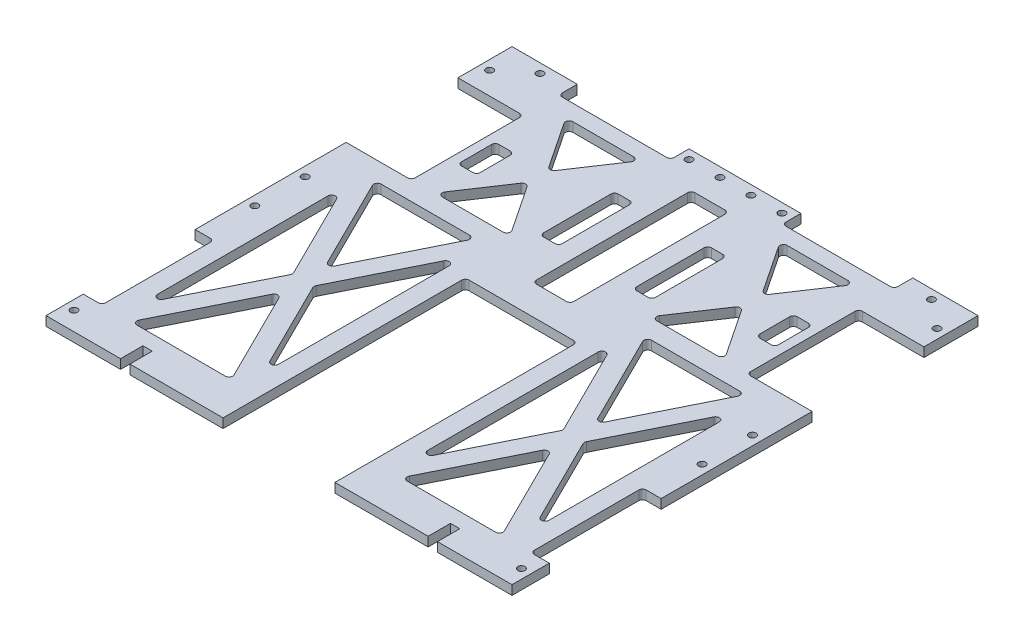
SolidWorks part; units mm, degrees
material "7050-T73510"
ref_plane "Front Plane" through (0, 0, 0) normal (0, 0, 1) x (1, 0, 0)
ref_plane "Top Plane" through (0, 0, 0) normal (0, 1, 0) x (1, 0, 0)
ref_plane "Right Plane" through (0, 0, 0) normal (1, 0, 0) x (0, 0, -1)
sketch "Sketch1" plane through (0, 0, 0) normal (0, 1, 0) x (1, 0, 0)
  line L0 (0, -55) -> (0, 55) construction
  line L1 (-158.75, -76.2) -> (158.75, -76.2)
  line L2 (-158.75, -76.2) -> (-158.75, 76.2)
  line L3 (-158.75, 76.2) -> (158.75, 76.2)
  line L4 (158.75, -76.2) -> (158.75, 76.2)
  line L5 (-158.75, -76.2) -> (158.75, 76.2) construction
  line L6 (-158.75, 76.2) -> (158.75, -76.2) construction
  line L7 (-158.75, -76.2) -> (-25.4, -76.2)
  line L8 (-158.75, -76.2) -> (-158.75, -241.3)
  line L9 (-158.75, -241.3) -> (-25.4, -241.3)
  line L10 (-25.4, -76.2) -> (-25.4, -241.3)
  line L11 (25.4, -76.2) -> (25.4, -241.3)
  line L12 (158.75, -241.3) -> (25.4, -241.3)
  line L13 (158.75, -76.2) -> (158.75, -241.3)
  line L14 (158.75, -76.2) -> (25.4, -76.2)
  line L15 (-38.1, -76.2) -> (-38.1, -241.3)
  line L16 (38.1, -76.2) -> (38.1, -241.3)
  point P0 (0, 0)
  dimension "D1" = 317.5
  dimension "D2" = 152.4
  dimension "D3" = 317.5
  dimension "D4" = 50.8
  dimension "D5" = 12.7
extrude "Boss-Extrude1" add sketch "Sketch1" along normal blind 6.35 contours L15 L1 L8 L9 | L14 L16 L12 L13 | L1 L7 L14 L4 L3 L2 region at (0, 0, 0) region at (-98.425, 0, 158.75) region at (98.425, 0, 158.75)
sketch "Sketch2" plane through (0, 6.35, 0) normal (0, 1, 0) x (1, 0, 0)
  line L0 (158.75, -241.3) -> (158.75, 76.2) construction
  line L1 (158.75, 39.37) -> (114.3, 39.37)
  line L2 (158.75, 39.37) -> (158.75, -36.83)
  line L3 (158.75, -36.83) -> (114.3, -36.83)
  line L4 (114.3, 39.37) -> (114.3, -36.83)
  line L5 (-158.75, 76.2) -> (158.75, 76.2) construction
  line L6 (158.75, -139.7) -> (146.05, -139.7)
  line L7 (158.75, -139.7) -> (158.75, -215.9)
  line L8 (158.75, -215.9) -> (146.05, -215.9)
  line L9 (146.05, -139.7) -> (146.05, -215.9)
  line L10 (0, -55) -> (0, 55) construction
  line L11 (-158.75, -215.9) -> (-146.05, -215.9)
  line L12 (-146.05, -139.7) -> (-146.05, -215.9)
  line L13 (-158.75, -139.7) -> (-146.05, -139.7)
  line L14 (-158.75, -139.7) -> (-158.75, -215.9)
  line L15 (-158.75, -36.83) -> (-114.3, -36.83)
  line L16 (-114.3, 39.37) -> (-114.3, -36.83)
  line L17 (-158.75, 39.37) -> (-114.3, 39.37)
  line L18 (-158.75, 39.37) -> (-158.75, -36.83)
  line L19 (-114.3, 63.5) -> (-38.1, 63.5)
  line L20 (114.3, 76.2) -> (38.1, 76.2)
  line L21 (114.3, 76.2) -> (114.3, 63.5)
  line L22 (114.3, 63.5) -> (38.1, 63.5)
  line L23 (38.1, 76.2) -> (38.1, 63.5)
  line L24 (-38.1, 76.2) -> (-38.1, 63.5)
  line L25 (-114.3, 76.2) -> (-38.1, 76.2)
  line L26 (-114.3, 76.2) -> (-114.3, 63.5)
  dimension "D1" = 44.45
  dimension "D2" = 12.7
  dimension "D3" = 76.2
  dimension "D4" = 76.2
  dimension "D5" = 36.83
  dimension "D6" = 215.9
  dimension "D7" = 76.2
  dimension "D8" = 12.7
  dimension "D9" = 76.2
extrude "Cut-Extrude1" cut sketch "Sketch2" against normal through all
sketch "Sketch4" plane through (0, 6.35, 0) normal (0, 1, 0) x (1, 0, 0)
  line L0 (38.1, -76.2) -> (38.1, -241.3) construction
  line L1 (50.8, -215.9) -> (133.35, -215.9)
  line L2 (50.8, -215.9) -> (50.8, -49.53)
  line L3 (50.8, -49.53) -> (133.35, -49.53)
  line L4 (133.35, -215.9) -> (133.35, -49.53)
  line L5 (146.05, -139.7) -> (146.05, -215.9) construction
  line L6 (158.75, -241.3) -> (38.1, -241.3) construction
  line L7 (50.8, -215.9) -> (133.35, -49.53) construction
  line L8 (50.8, -49.53) -> (133.35, -215.9) construction
  line L9 (133.35, -201.6135) -> (57.8887, -49.53)
  line L10 (126.2613, -215.9) -> (50.8, -63.8165)
  line L11 (50.8, -201.6135) -> (126.2613, -49.53)
  line L12 (57.8887, -215.9) -> (133.35, -63.8165)
  line L13 (114.3, -36.83) -> (158.75, -36.83) construction
  line L14 (0, -55) -> (0, 55) construction
  line L15 (-50.8, -201.6135) -> (-126.2613, -49.53)
  line L16 (-126.2613, -215.9) -> (-50.8, -63.8165)
  line L17 (-133.35, -201.6135) -> (-57.8887, -49.53)
  line L18 (-57.8887, -215.9) -> (-133.35, -63.8165)
  line L19 (-50.8, -49.53) -> (-133.35, -49.53)
  line L20 (-133.35, -215.9) -> (-133.35, -49.53)
  line L21 (-50.8, -215.9) -> (-133.35, -215.9)
  line L22 (-50.8, -215.9) -> (-50.8, -49.53)
  point P18 (116.2026, -167.0549)
  dimension "D1" = 12.7
  dimension "D2" = 12.7
  dimension "D3" = 25.4
  dimension "D4" = 12.7
  dimension "D5" = 12.7
extrude "Cut-Extrude3" cut sketch "Sketch4" against normal through all contours L12 L9 L4 | L12 L1 L10 | L2 L11 L10 | L9 L11 L3 | L21 L18 L16 | L20 L17 L18 | L17 L19 L15 | L15 L22 L16 region at (92.075, 6.35, 192.9338) region at (62.1954, 6.35, 132.715) region at (121.9546, 6.35, 132.715) region at (92.075, 6.35, 72.4962) region at (-62.1954, 6.35, 132.715) region at (-92.075, 6.35, 72.4962) region at (-92.075, 6.35, 192.9338) region at (-121.9546, 6.35, 132.715)
sketch "Sketch3" plane through (0, 6.35, 0) normal (0, 1, 0) x (1, 0, 0)
  line L0 (-38.1, -76.2) -> (38.1, -76.2) construction
  line L1 (-38.1, -25.4) -> (-25.4, -25.4)
  line L2 (-38.1, -25.4) -> (-38.1, 25.4)
  line L3 (-38.1, 25.4) -> (-25.4, 25.4)
  line L4 (-25.4, -25.4) -> (-25.4, 25.4)
  line L5 (0, -3.4925) -> (0, 3.4925) construction
  line L6 (38.1, 25.4) -> (25.4, 25.4)
  line L7 (25.4, -25.4) -> (25.4, 25.4)
  line L8 (38.1, -25.4) -> (25.4, -25.4)
  line L9 (38.1, -25.4) -> (38.1, 25.4)
  line L10 (114.3, 39.37) -> (114.3, -36.83) construction
  line L11 (95.25, 13.97) -> (107.95, 13.97)
  line L12 (95.25, 13.97) -> (95.25, -11.43)
  line L13 (95.25, -11.43) -> (107.95, -11.43)
  line L14 (107.95, 13.97) -> (107.95, -11.43)
  line L15 (38.1, 63.5) -> (114.3, 63.5) construction
  line L16 (-95.25, -11.43) -> (-107.95, -11.43)
  line L17 (-107.95, 13.97) -> (-107.95, -11.43)
  line L18 (-95.25, 13.97) -> (-107.95, 13.97)
  line L19 (-95.25, 13.97) -> (-95.25, -11.43)
  line L20 (158.75, -241.3) -> (38.1, -241.3) construction
  line L21 (107.95, -241.3) -> (101.6, -241.3)
  line L22 (107.95, -241.3) -> (107.95, -226.06)
  line L23 (107.95, -226.06) -> (101.6, -226.06)
  line L24 (101.6, -241.3) -> (101.6, -226.06)
  line L25 (158.75, -241.3) -> (158.75, -215.9) construction
  line L26 (-101.6, -241.3) -> (-101.6, -226.06)
  line L27 (-107.95, -226.06) -> (-101.6, -226.06)
  line L28 (-107.95, -241.3) -> (-107.95, -226.06)
  line L29 (-107.95, -241.3) -> (-101.6, -241.3)
  dimension "D1" = 50.8
  dimension "D2" = 12.7
  dimension "D3" = 50.8
  dimension "D4" = 50.8
  dimension "D5" = 25.4
  dimension "D6" = 12.7
  dimension "D7" = 6.35
  dimension "D8" = 49.53
  dimension "D9" = 50.8
  dimension "D10" = 6.35
  dimension "D11" = 15.24
extrude "Cut-Extrude2" cut sketch "Sketch3" against normal through all
sketch "Sketch7" plane through (0, 6.35, 0) normal (0, 1, 0) x (1, 0, 0)
  line L0 (158.75, -139.7) -> (146.05, -139.7) construction
  line L1 (158.75, -139.7) -> (158.75, -36.83) construction
  line L2 (0, -3.4925) -> (0, 3.4925) construction
  line L3 (158.75, -241.3) -> (107.95, -241.3) construction
  line L4 (-38.1, 76.2) -> (-38.1, 63.5) construction
  line L6 (-38.1, 76.2) -> (38.1, 76.2) construction
  circle A0 centre (152.4, -105.41) radius 2.413
  circle A1 centre (152.4, -71.12) radius 2.413
  circle A8 centre (152.4, -228.6) radius 2.413
  circle A10 centre (133.35, 69.85) radius 2.413
  circle A12 centre (152.4, 54.61) radius 2.413
  circle A19 centre (-152.4, -228.6) radius 2.413
  circle A20 centre (-31.75, 69.85) radius 2.413
  circle A21 centre (-10.668, 69.85) radius 2.413
  circle A22 centre (10.414, 69.85) radius 2.413
  circle A23 centre (31.496, 69.85) radius 2.413
  circle A24 centre (-152.4, 54.61) radius 2.413
  circle A25 centre (-133.35, 69.85) radius 2.413
  circle A27 centre (-152.4, -71.12) radius 2.413
  circle A28 centre (-152.4, -105.41) radius 2.413
  dimension "D1" = 4.826
  dimension "D3" = 6.35
  dimension "D5" = 12.7
  dimension "D9" = 4.826
  dimension "D2" = 34.29
  dimension "D10" = 6.35
  dimension "D11" = 6.35
  dimension "D4" = 2
  dimension "D12" = 4
extrude "Cut-Extrude6" cut sketch "Sketch7" against normal through all
sketch "Sketch12" plane through (0, 6.35, 0) normal (0, 1, 0) x (1, 0, 0)
  line L0 (-98.425, 52.6142) -> (-47.625, 52.6142)
  line L1 (-47.625, 52.6142) -> (-73.025, 14.5142)
  line L2 (-73.025, 14.5142) -> (-98.425, 52.6142)
  line L3 (-94.4842, 8.1642) -> (-61.9728, 8.1642) construction
  line L4 (-114.3, 39.37) -> (-114.3, -36.83) construction
  line L5 (-47.625, -36.2858) -> (-73.025, 1.8142)
  line L6 (-98.425, -36.2858) -> (-47.625, -36.2858)
  line L7 (-73.025, 1.8142) -> (-98.425, -36.2858)
  line L8 (0, -55) -> (0, 55) construction
  line L9 (94.4842, 8.1642) -> (61.9728, 8.1642) construction
  line L10 (73.025, 1.8142) -> (98.425, -36.2858)
  line L11 (98.425, -36.2858) -> (47.625, -36.2858)
  line L12 (47.625, -36.2858) -> (73.025, 1.8142)
  line L13 (73.025, 14.5142) -> (98.425, 52.6142)
  line L14 (47.625, 52.6142) -> (73.025, 14.5142)
  line L15 (98.425, 52.6142) -> (47.625, 52.6142)
  line L23 (-12.7, -55.6542) -> (12.7, -55.6542)
  line L24 (-12.7, -55.6542) -> (-12.7, 52.2958)
  line L25 (-12.7, 52.2958) -> (12.7, 52.2958)
  line L26 (12.7, -55.6542) -> (12.7, 52.2958)
  point P6 (-73.025, 52.6142)
  point P25 (0, -55.6542)
  dimension "D1" = 6.35
  dimension "D2" = 44.45
  dimension "D3" = 50.8
  dimension "D4" = 41.275
  dimension "D5" = 25.4
  dimension "D6" = 107.95
extrude "Cut-Extrude9" cut sketch "Sketch12" against normal through all
fillet "Fillet1" radius 2.54 20 edges at (-12.7, 3.175, 55.6542) (-12.7, 3.175, -52.2958) (-133.35, 3.175, 63.8165) (-133.35, 3.175, 201.6135) (-126.2613, 3.175, 215.9) (-57.8887, 3.175, 215.9) (-92.075, 3.175, 147.0015) (-84.9863, 3.175, 132.715) (-50.8, 3.175, 63.8165) (-50.8, 3.175, 201.6135) (-92.075, 3.175, 118.4285) (-99.1637, 3.175, 132.715) (-57.8887, 3.175, 49.53) (-126.2613, 3.175, 49.53) (-98.425, 3.175, 36.2858) (-47.625, 3.175, 36.2858) (-73.025, 3.175, -1.8142) (-73.025, 3.175, -14.5142) (-47.625, 3.175, -52.6142) (-98.425, 3.175, -52.6142)
fillet "Fillet2" radius 2.54 20 edges at (50.8, 3.175, 63.8165) (133.35, 3.175, 63.8165) (92.075, 3.175, 147.0015) (99.1637, 3.175, 132.715) (50.8, 3.175, 201.6135) (57.8887, 3.175, 215.9) (133.35, 3.175, 201.6135) (84.9863, 3.175, 132.715) (126.2613, 3.175, 215.9) (92.075, 3.175, 118.4285) (57.8887, 3.175, 49.53) (126.2613, 3.175, 49.53) (73.025, 3.175, -1.8142) (47.625, 3.175, 36.2858) (98.425, 3.175, 36.2858) (98.425, 3.175, -52.6142) (73.025, 3.175, -14.5142) (12.7, 3.175, 55.6542) (12.7, 3.175, -52.2958) (47.625, 3.175, -52.6142)
fillet "Fillet3" radius 2.54 30 edges at (-107.95, 3.175, 11.43) (-95.25, 3.175, 11.43) (-95.25, 3.175, -13.97) (-107.95, 3.175, -13.97) (95.25, 3.175, 11.43) (107.95, 3.175, 11.43) (107.95, 3.175, -13.97) (95.25, 3.175, -13.97) (114.3, 3.175, -63.5) (38.1, 3.175, -63.5) (-38.1, 3.175, -63.5) (-114.3, 3.175, -63.5) (146.05, 3.175, 215.9) (146.05, 3.175, 139.7) (-146.05, 3.175, 215.9) (-146.05, 3.175, 139.7) (38.1, 3.175, 76.2) (-38.1, 3.175, 76.2) (-114.3, 3.175, 36.83) (-114.3, 3.175, -39.37) (114.3, 3.175, -39.37) (114.3, 3.175, 36.83) (-25.4, 3.175, 25.4) (-38.1, 3.175, 25.4) (-38.1, 3.175, -25.4) (-25.4, 3.175, -25.4) (25.4, 3.175, 25.4) (38.1, 3.175, 25.4) (38.1, 3.175, -25.4) (25.4, 3.175, -25.4)
